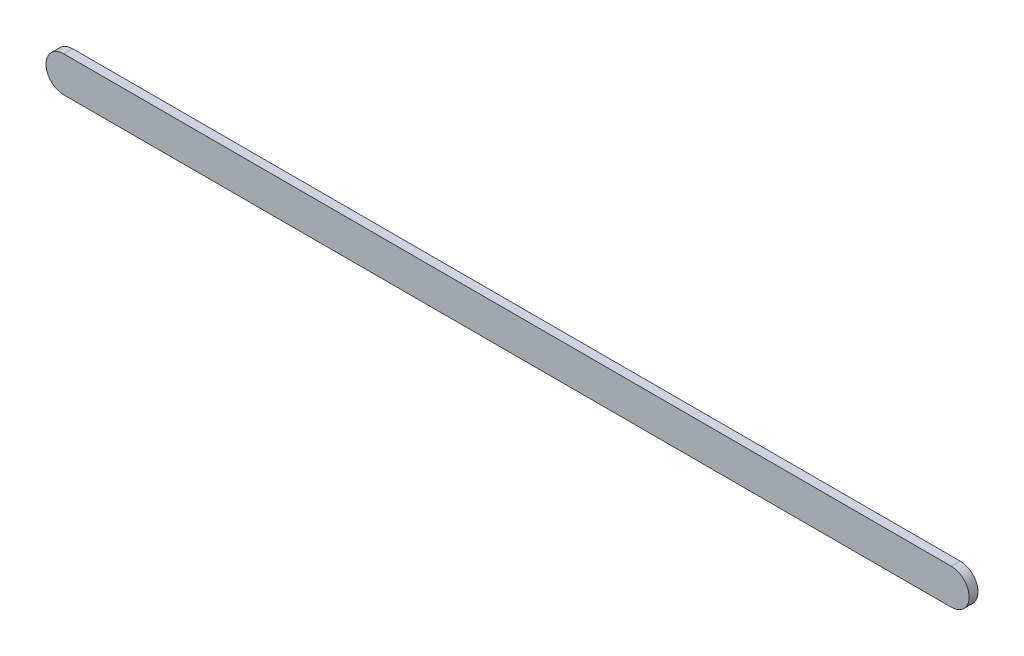
SolidWorks part; units mm, degrees
ref_plane "Front Plane" through (0, 0, 0) normal (0, 0, 1) x (1, 0, 0)
ref_plane "Top Plane" through (0, 0, 0) normal (0, 1, 0) x (1, 0, 0)
ref_plane "Right Plane" through (0, 0, 0) normal (1, 0, 0) x (0, 0, -1)
sketch "Sketch3" plane through (0, 0, 0) normal (0, 0, 1) x (1, 0, 0)
  line L0 (0, 0) -> (250, 0) construction
  line L1 (0, 5) -> (250, 5)
  line L2 (0, -5) -> (250, -5)
  arc A0 (0, 5) -> (0, -5) centre (0, 0) ccw
  arc A1 (250, -5) -> (250, 5) centre (250, 0) ccw
  point P3 (125, 0)
extrude "Boss-Extrude1" add sketch "Sketch3" along normal blind 2.5
ref_axis "Axis1" through (250, 0, 2.5) along (0, 0, -1)
ref_axis "Axis2" through (0, 0, 2.5) along (0, 0, -1)
